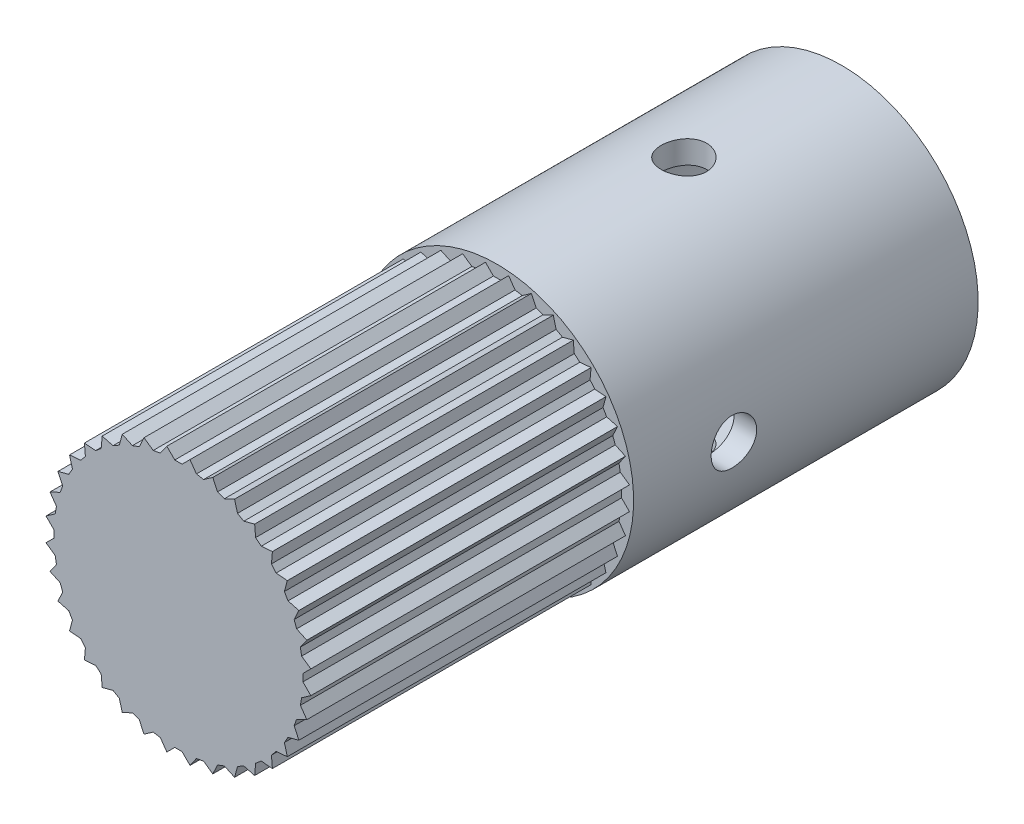
SolidWorks part; units mm, degrees
material "AISI 1015 Steel, Cold Drawn (SS)"
ref_plane "X-Y Datum" through (0, 0, 0) normal (0, 0, 1) x (1, 0, 0)
ref_plane "X-Z Datum" through (0, 0, 0) normal (0, 1, 0) x (1, 0, 0)
ref_plane "Y-Z Datum" through (0, 0, 0) normal (1, 0, 0) x (0, 0, -1)
sketch "Sketch9" plane through (0, 0, 0) normal (0, 1, 0) x (1, 0, 0)
  line L0 (16.002, 0) -> (0, 0)
  line L1 (0, 0) -> (0, -389.0916)
  line L2 (0, -389.0916) -> (-72.2493, -524.9728)
  dimension "D1" = 153.895
  dimension "D2" = 28
  dimension "D3" = 389.0916
  dimension "D5" = 16.002
sketch "Sketch5" plane through (0, 0, 0) normal (0, 1, 0) x (1, 0, 0)
  line L0 (7.9375, -68.4166) -> (7.9375, -22.1615)
  line L1 (7.9375, -22.1615) -> (9.525, -22.1615)
  line L2 (9.525, -22.1615) -> (9.525, -68.4166)
  line L3 (9.525, -68.4166) -> (7.9375, -68.4166)
  line L5 (16.002, 0) -> (0, 0) construction
  line L6 (0, 0) -> (0, -389.0916) construction
  line L7 (0, -389.0916) -> (9.525, -389.0916) construction
  line L8 (12.5602, -49.1666) -> (0, -49.1666) construction
  dimension "D1" = 1.5875
  dimension "D2" = 22.1615
  dimension "D3" = 7.9375
  dimension "D4" = 339.925
  dimension "D5" = 320.675
revolve "Revolve2" add sketch "Sketch5" angle 360 about L1
sketch "Sketch6" plane through (0, 0, 0) normal (0, 1, 0) x (1, 0, 0)
  circle A0 centre (0, -33.1635) radius 1.5875 construction
  circle A1 centre (0, -33.1635) radius 1.5875
sketch "Sketch7" plane through (0, 0, 0) normal (1, 0, 0) x (0, 0, -1)
  circle A2 centre (-39.196, 0) radius 1.5875
  circle A4 centre (-39.196, 0) radius 1.5875 construction
extrude "Cut-Extrude5" cut sketch "Sketch7" against normal through all both and the other way through all
extrude "Cut-Extrude6" cut sketch "Sketch6" against normal through all both and the other way through all
sketch "Sketch8" plane through (0, 0, 0) normal (0, 0, 1) x (1, 0, 0)
  line L0 (9.2357, -0.808) -> (8.6817, -0.254)
  line L1 (8.6817, -0.254) -> (8.6817, 0.254)
  line L2 (8.6817, 0.254) -> (9.2357, 0.808)
  line L3 (8.6817, 0) -> (0, 0) construction
  line L4 (8.9551, -2.3995) -> (8.5057, -1.7577)
  line L5 (8.5057, -1.7577) -> (8.5939, -1.2574)
  line L6 (8.5939, -1.2574) -> (9.2357, -0.808)
  line L7 (8.4024, -3.9181) -> (8.0713, -3.208)
  line L8 (8.0713, -3.208) -> (8.245, -2.7306)
  line L9 (8.245, -2.7306) -> (8.9551, -2.3995)
  line L10 (7.5944, -5.3176) -> (7.3916, -4.5608)
  line L11 (7.3916, -4.5608) -> (7.6456, -4.1209)
  line L12 (7.6456, -4.1209) -> (8.4024, -3.9181)
  line L13 (6.5556, -6.5556) -> (6.4873, -5.7751)
  line L14 (6.4873, -5.7751) -> (6.8138, -5.3859)
  line L15 (6.8138, -5.3859) -> (7.5944, -5.3176)
  line L16 (5.3176, -7.5944) -> (5.3859, -6.8138)
  line L17 (5.3859, -6.8138) -> (5.7751, -6.4873)
  line L18 (5.7751, -6.4873) -> (6.5556, -6.5556)
  line L19 (3.9181, -8.4024) -> (4.1209, -7.6456)
  line L20 (4.1209, -7.6456) -> (4.5608, -7.3916)
  line L21 (4.5608, -7.3916) -> (5.3176, -7.5944)
  line L22 (2.3995, -8.9551) -> (2.7306, -8.245)
  line L23 (2.7306, -8.245) -> (3.208, -8.0713)
  line L24 (3.208, -8.0713) -> (3.9181, -8.4024)
  line L25 (0.808, -9.2357) -> (1.2574, -8.5939)
  line L26 (1.2574, -8.5939) -> (1.7577, -8.5057)
  line L27 (1.7577, -8.5057) -> (2.3995, -8.9551)
  line L28 (-0.808, -9.2357) -> (-0.254, -8.6817)
  line L29 (-0.254, -8.6817) -> (0.254, -8.6817)
  line L30 (0.254, -8.6817) -> (0.808, -9.2357)
  line L31 (-2.3995, -8.9551) -> (-1.7577, -8.5057)
  line L32 (-1.7577, -8.5057) -> (-1.2574, -8.5939)
  line L33 (-1.2574, -8.5939) -> (-0.808, -9.2357)
  line L34 (-3.9181, -8.4024) -> (-3.208, -8.0713)
  line L35 (-3.208, -8.0713) -> (-2.7306, -8.245)
  line L36 (-2.7306, -8.245) -> (-2.3995, -8.9551)
  line L37 (-5.3176, -7.5944) -> (-4.5608, -7.3916)
  line L38 (-4.5608, -7.3916) -> (-4.1209, -7.6456)
  line L39 (-4.1209, -7.6456) -> (-3.9181, -8.4024)
  line L40 (-6.5556, -6.5556) -> (-5.7751, -6.4873)
  line L41 (-5.7751, -6.4873) -> (-5.3859, -6.8138)
  line L42 (-5.3859, -6.8138) -> (-5.3176, -7.5944)
  line L43 (-7.5944, -5.3176) -> (-6.8138, -5.3859)
  line L44 (-6.8138, -5.3859) -> (-6.4873, -5.7751)
  line L45 (-6.4873, -5.7751) -> (-6.5556, -6.5556)
  line L46 (-8.4024, -3.9181) -> (-7.6456, -4.1209)
  line L47 (-7.6456, -4.1209) -> (-7.3916, -4.5608)
  line L48 (-7.3916, -4.5608) -> (-7.5944, -5.3176)
  line L49 (-8.9551, -2.3995) -> (-8.245, -2.7306)
  line L50 (-8.245, -2.7306) -> (-8.0713, -3.208)
  line L51 (-8.0713, -3.208) -> (-8.4024, -3.9181)
  line L52 (-9.2357, -0.808) -> (-8.5939, -1.2574)
  line L53 (-8.5939, -1.2574) -> (-8.5057, -1.7577)
  line L54 (-8.5057, -1.7577) -> (-8.9551, -2.3995)
  line L55 (-9.2357, 0.808) -> (-8.6817, 0.254)
  line L56 (-8.6817, 0.254) -> (-8.6817, -0.254)
  line L57 (-8.6817, -0.254) -> (-9.2357, -0.808)
  line L58 (-8.9551, 2.3995) -> (-8.5057, 1.7577)
  line L59 (-8.5057, 1.7577) -> (-8.5939, 1.2574)
  line L60 (-8.5939, 1.2574) -> (-9.2357, 0.808)
  line L61 (-8.4024, 3.9181) -> (-8.0713, 3.208)
  line L62 (-8.0713, 3.208) -> (-8.245, 2.7306)
  line L63 (-8.245, 2.7306) -> (-8.9551, 2.3995)
  line L64 (-7.5944, 5.3176) -> (-7.3916, 4.5608)
  line L65 (-7.3916, 4.5608) -> (-7.6456, 4.1209)
  line L66 (-7.6456, 4.1209) -> (-8.4024, 3.9181)
  line L67 (-6.5556, 6.5556) -> (-6.4873, 5.7751)
  line L68 (-6.4873, 5.7751) -> (-6.8138, 5.3859)
  line L69 (-6.8138, 5.3859) -> (-7.5944, 5.3176)
  line L70 (-5.3176, 7.5944) -> (-5.3859, 6.8138)
  line L71 (-5.3859, 6.8138) -> (-5.7751, 6.4873)
  line L72 (-5.7751, 6.4873) -> (-6.5556, 6.5556)
  line L73 (-3.9181, 8.4024) -> (-4.1209, 7.6456)
  line L74 (-4.1209, 7.6456) -> (-4.5608, 7.3916)
  line L75 (-4.5608, 7.3916) -> (-5.3176, 7.5944)
  line L76 (-2.3995, 8.9551) -> (-2.7306, 8.245)
  line L77 (-2.7306, 8.245) -> (-3.208, 8.0713)
  line L78 (-3.208, 8.0713) -> (-3.9181, 8.4024)
  line L79 (-0.808, 9.2357) -> (-1.2574, 8.5939)
  line L80 (-1.2574, 8.5939) -> (-1.7577, 8.5057)
  line L81 (-1.7577, 8.5057) -> (-2.3995, 8.9551)
  line L82 (0.808, 9.2357) -> (0.254, 8.6817)
  line L83 (0.254, 8.6817) -> (-0.254, 8.6817)
  line L84 (-0.254, 8.6817) -> (-0.808, 9.2357)
  line L85 (2.3995, 8.9551) -> (1.7577, 8.5057)
  line L86 (1.7577, 8.5057) -> (1.2574, 8.5939)
  line L87 (1.2574, 8.5939) -> (0.808, 9.2357)
  line L88 (3.9181, 8.4024) -> (3.208, 8.0713)
  line L89 (3.208, 8.0713) -> (2.7306, 8.245)
  line L90 (2.7306, 8.245) -> (2.3995, 8.9551)
  line L91 (5.3176, 7.5944) -> (4.5608, 7.3916)
  line L92 (4.5608, 7.3916) -> (4.1209, 7.6456)
  line L93 (4.1209, 7.6456) -> (3.9181, 8.4024)
  line L94 (6.5556, 6.5556) -> (5.7751, 6.4873)
  line L95 (5.7751, 6.4873) -> (5.3859, 6.8138)
  line L96 (5.3859, 6.8138) -> (5.3176, 7.5944)
  line L97 (7.5944, 5.3176) -> (6.8138, 5.3859)
  line L98 (6.8138, 5.3859) -> (6.4873, 5.7751)
  line L99 (6.4873, 5.7751) -> (6.5556, 6.5556)
  line L100 (8.4024, 3.9181) -> (7.6456, 4.1209)
  line L101 (7.6456, 4.1209) -> (7.3916, 4.5608)
  line L102 (7.3916, 4.5608) -> (7.5944, 5.3176)
  line L103 (8.9551, 2.3995) -> (8.245, 2.7306)
  line L104 (8.245, 2.7306) -> (8.0713, 3.208)
  line L105 (8.0713, 3.208) -> (8.4024, 3.9181)
  line L106 (9.2357, 0.808) -> (8.5939, 1.2574)
  line L107 (8.5939, 1.2574) -> (8.5057, 1.7577)
  line L108 (8.5057, 1.7577) -> (8.9551, 2.3995)
  circle A0 centre (0, 0) radius 12.7
  circle A1 centre (0, 0) radius 9.271 construction
  circle A2 centre (0, 0) radius 8.6854 construction
  point P153 (0, 0)
  dimension "D1" = 25.4
  dimension "D4" = 18.542
  dimension "D6" = 17.3708
  dimension "D2" = 0.508
  dimension "D3" = 135
  dimension "D5" = 36
extrude "Cut-Extrude7" cut sketch "Sketch8" against normal blind 22.225 from surface starting at face at (-9.525, 0, 68.4166)
ref_plane "Plane1" through (0, 0, 47.5615) normal (0, 0, -1) x (-1, 0, 0)
sketch "Sketch10" plane through (0, 0, 47.5615) normal (0, 0, -1) x (-1, 0, 0)
  circle A0 centre (0, 0) radius 7.9375
  dimension "D1" = 15.875
extrude "Boss-Extrude1" add sketch "Sketch10" against normal up to surface (20.8551 mm away) up to face at (-7.9375, 0, 68.4166)
sketch "Sketch11" plane through (0, 0, 22.1615) normal (0, 0, -1) x (-1, 0, 0)
  line L0 (0, 9.525) -> (13.3548, 9.525) construction
  line L1 (0, 9.525) -> (0, 15.4312) construction
  line L2 (-9.525, 0) -> (-9.525, 9.1744) construction
  line L3 (-9.525, 0) -> (-16.674, 0) construction
  circle A0 centre (0, 0) radius 9.525 construction
  point P0 (0, 9.525)
  point P1 (-9.525, 0)
